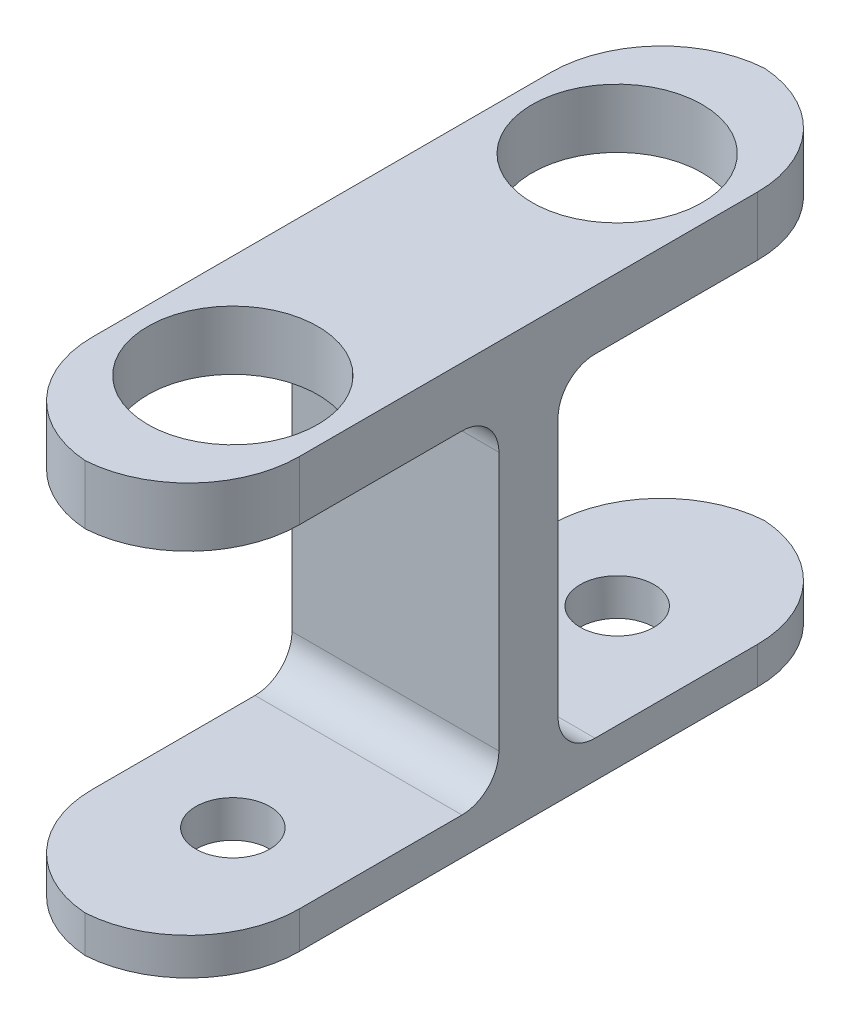
SolidWorks part; units mm, degrees
ref_plane "Front Plane" through (0, 0, 0) normal (0, 0, 1) x (1, 0, 0)
ref_plane "Top Plane" through (0, 0, 0) normal (0, 1, 0) x (1, 0, 0)
ref_plane "Right Plane" through (0, 0, 0) normal (1, 0, 0) x (0, 0, -1)
sketch "Sketch1" plane through (0, 0, 0) normal (1, 0, 0) x (0, 0, -1)
  line L0 (0, 0) -> (42, 0)
  line L1 (42, 0) -> (42, -45)
  line L2 (42, -45) -> (0, -45)
  line L3 (0, -45) -> (0, -50)
  line L4 (0, -50) -> (46, -50)
  line L5 (46, -50) -> (46, 8)
  line L6 (46, 8) -> (0, 8)
  line L7 (0, 8) -> (0, 0)
  dimension "D1" = 42
  dimension "D2" = 45
  dimension "D3" = 8
  dimension "D4" = 4
  dimension "D5" = 5
extrude "Boss-Extrude1" add sketch "Sketch1" along normal blind 28 contours L0 L1 L2 L3 L4 L5 L6 L7
sketch "Sketch2" plane through (0, 8, 0) normal (0, 1, 0) x (1, 0, 0)
  line L0 (28, 0) -> (0, 0) construction
  circle A0 centre (14, 20) radius 11.5
  point P2 (14, 0)
  dimension "D1" = 23
  dimension "D2" = 20
extrude "Cut-Extrude1" cut sketch "Sketch2" against normal up to next
sketch "Sketch3" plane through (0, -45, 0) normal (0, 1, 0) x (1, 0, 0)
  circle A0 centre (14, 20) radius 5
  circle A1 centre (14, 20) radius 11.5 construction
  dimension "D1" = 10
extrude "Cut-Extrude2" cut sketch "Sketch3" against normal up to next contours A0
fillet "Fillet2" radius 5 2 edges at (14, 0, -42) (14, -45, -42)
mirror "Mirror2" about plane through (28, -50, -46) normal (0, 0, 1) of "Fillet2", "Boss-Extrude1", "Cut-Extrude1", "Cut-Extrude2"
fillet "Fillet3" radius 15 8 edges at (28, -47.5, 0) (0, -47.5, 0) (28, 4, 0) (0, 4, 0) (0, 4, -92) (0, -47.5, -92) (28, -47.5, -92) (28, 4, -92)
